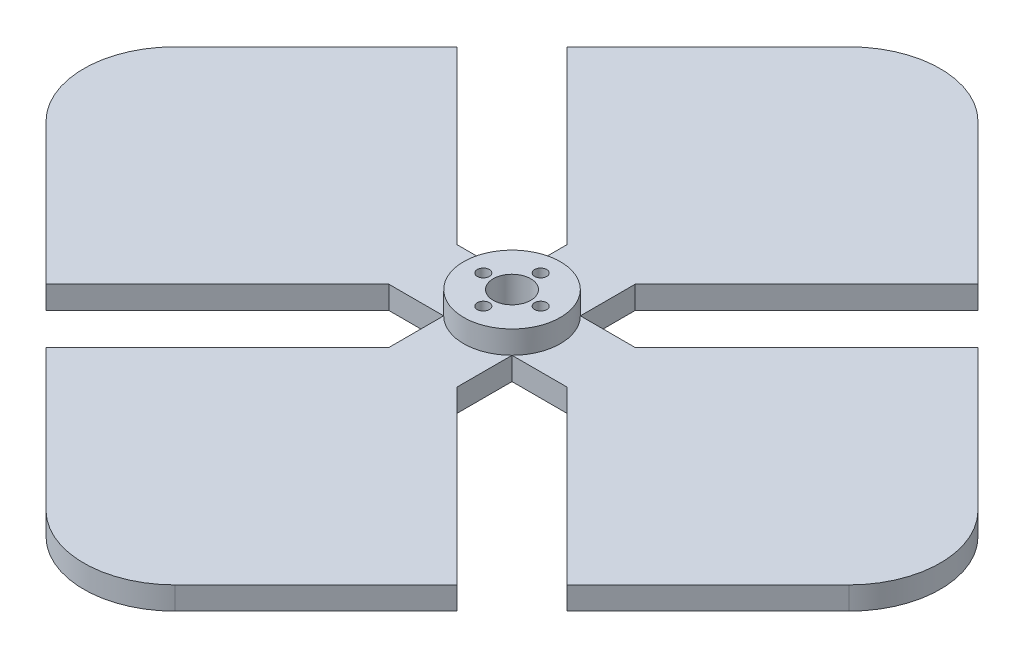
SolidWorks part; units mm, degrees
ref_plane "Front Plane" through (0, 0, 0) normal (0, 0, 1) x (1, 0, 0)
ref_plane "Top Plane" through (0, 0, 0) normal (0, 1, 0) x (1, 0, 0)
ref_plane "Right Plane" through (0, 0, 0) normal (1, 0, 0) x (0, 0, -1)
sketch "Sketch4" plane through (0, 0, 0) normal (0, 1, 0) x (1, 0, 0)
  line L8 (15.3035, 0) -> (72.5975, -57.294)
  line L9 (15.3035, 0) -> (72.5975, 57.294)
  line L10 (72.5975, -57.294) -> (129.8916, 0)
  line L11 (72.5975, 57.294) -> (129.8916, 0)
  line L13 (0, 9.525) -> (24.8285, 9.525)
  line L14 (0, 9.525) -> (0, -9.525)
  line L15 (0, -9.525) -> (24.8285, -9.525)
  line L16 (24.8285, 9.525) -> (24.8285, -9.525)
  dimension "D1" = 81.026
  dimension "D2" = 15.3035
  dimension "D3" = 19.05
extrude "Boss-Extrude5" add sketch "Sketch4" along normal blind 6.35 contours L9 L16 L8 L10 L11 | L16 L9 L8 | L14 L15 L8 L9 L13 region at (21.6535, 0, 0) region at (10.2214, 0, 0) region at (73.3114, 0, 0)
sketch "Sketch6" plane through (0, 0, 0) normal (0, 0, 1) x (1, 0, 0)
  line L0 (0, 0) -> (0, 27.64) construction
fillet "Fillet1" radius 25.4 1 edges at (129.8916, 3.175, 0)
pattern_circular "CirPattern7" count 4 over 360 about axis through (0, 0, 0) along (0, 1, 0) of "Boss-Extrude5", "Fillet1"
sketch "Sketch13" plane through (0, 6.35, 0) normal (0, 1, 0) x (1, 0, 0)
  circle A0 centre (0, 0) radius 13.4704
extrude "Boss-Extrude8" add sketch "Sketch13" along normal blind 6.35
sketch "Sketch1" plane through (0, 0, 0) normal (0, 1, 0) x (1, 0, 0)
  circle A0 centre (0, 0) radius 2.6905 construction
  circle A1 centre (0, 0) radius 5.227
  circle A2 centre (8, 0) radius 1.6865
  circle A6 centre (0, -8) radius 1.6865
  circle A7 centre (-8, 0) radius 1.6865
  circle A8 centre (0, 8) radius 1.6865
  point P15 (0, 0)
  dimension "D1" = 10.454
  dimension "D3" = 3.373
  dimension "D2" = 8
extrude "Cut-Extrude1" cut sketch "Sketch1" along normal through all
equation "\"tightTol\"= 0.005in"
equation "\"normTol\"= 0.01in"
equation "\"looseTol\"= 0.02in"
equation "\"D1@Sketch1\"=\"normTol\"+10.2mm"
equation "\"D2@Sketch1\"=8mm"
equation "\"D1@Sketch4\"=3.25-3*\"looseTol\""
equation "\"D2@Sketch4\"=9/16+2*\"looseTol\""
equation "\"D3@Sketch1\"=3.5mm-\"tightTol\""
